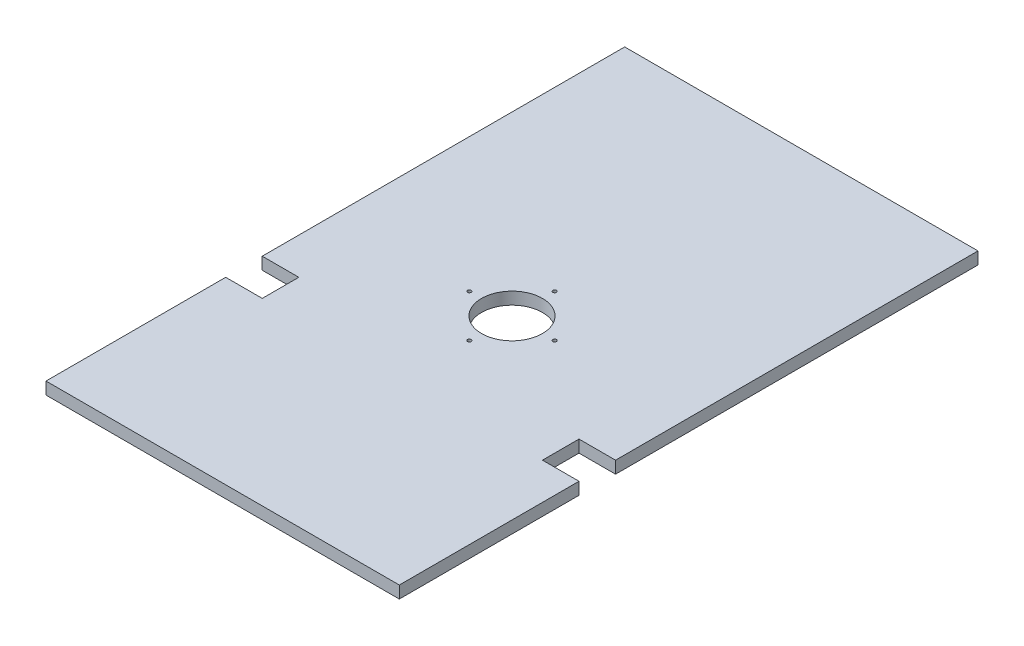
SolidWorks part; units mm, degrees
ref_plane "Alzado" through (0, 0, 0) normal (0, 0, 1) x (1, 0, 0)
ref_plane "Planta" through (0, 0, 0) normal (0, 1, 0) x (1, 0, 0)
ref_plane "Vista lateral" through (0, 0, 0) normal (1, 0, 0) x (0, 0, -1)
sketch "Croquis1" plane through (0, 0, 0) normal (0, 1, 0) x (1, 0, 0)
  line L0 (-145, -75) -> (-115, -75) construction
  line L1 (-145, 237.5) -> (145, 237.5)
  line L2 (-145, 237.5) -> (-145, -60)
  line L3 (-145, -237.5) -> (145, -237.5)
  line L4 (145, 237.5) -> (145, -60)
  line L5 (-145, 237.5) -> (145, -237.5) construction
  line L6 (-145, -237.5) -> (145, 237.5) construction
  line L7 (0, 35) -> (0, 0) construction
  line L8 (0, 0) -> (-35, 0) construction
  line L9 (-115, -90) -> (-115, -60)
  line L10 (-115, -60) -> (-145, -60)
  line L11 (-115, -90) -> (-145, -90)
  line L12 (-145, -90) -> (-145, -237.5)
  line L13 (115, -90) -> (145, -90)
  line L14 (115, -90) -> (115, -60)
  line L15 (115, -60) -> (145, -60)
  line L16 (145, -90) -> (145, -237.5)
  circle A0 centre (0, 35) radius 1.5
  circle A1 centre (-35, 0) radius 1.5
  circle A2 centre (0, -35) radius 1.5
  circle A3 centre (35, 0) radius 1.5
  point P0 (0, 0)
  point P14 (-115, -75)
  dimension "D8" = 3
  dimension "D1" = 290
  dimension "D2" = 475
  dimension "D3" = 30
  dimension "D4" = 30
  dimension "D5" = 60
  dimension "D6" = 35
  dimension "D7" = 35
extrude "Saliente-Extruir2" add sketch "Croquis1" along normal blind 10
sketch "Croquis3" plane through (0, 0, 0) normal (0, 1, 0) x (1, 0, 0)
  circle A0 centre (0, 0) radius 25
  dimension "D1" = 50
extrude "Cortar-Extruir1" cut sketch "Croquis3" against normal mid plane 20
